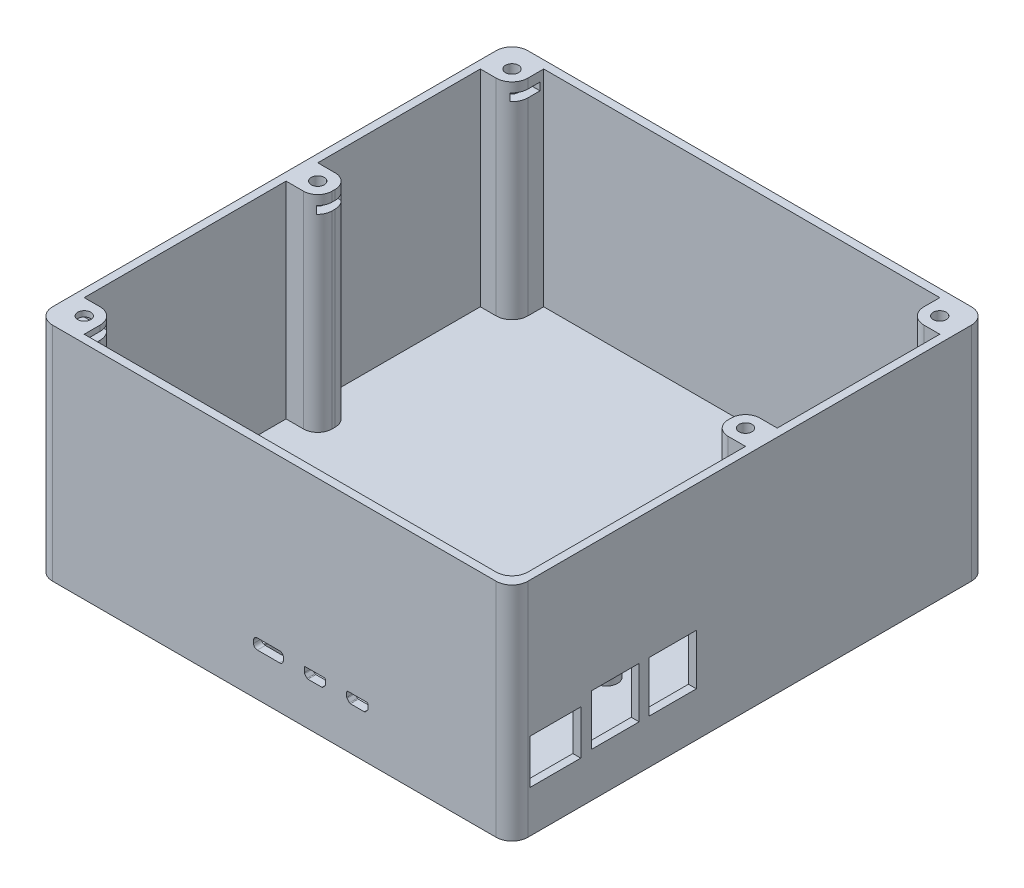
SolidWorks part; units mm, degrees
ref_plane "Alzado" through (0, 0, 0) normal (0, 0, 1) x (1, 0, 0)
ref_plane "Planta" through (0, 0, 0) normal (0, 1, 0) x (1, 0, 0)
ref_plane "Vista lateral" through (0, 0, 0) normal (1, 0, 0) x (0, 0, -1)
sketch "Croquis2" plane through (0, 0, 0) normal (0, 1, 0) x (1, 0, 0)
  line L1 (-75, -75) -> (75, -75)
  line L2 (-75, -75) -> (-75, 75)
  line L3 (-75, 75) -> (75, 75)
  line L4 (75, -75) -> (75, 75)
  line L5 (-75, -75) -> (75, 75) construction
  line L6 (-75, 75) -> (75, -75) construction
  point P0 (0, 0)
extrude "Saliente-Extruir1" add sketch "Croquis2" along normal blind 70
sketch "Croquis3" plane through (0, 70, 0) normal (0, 1, 0) x (1, 0, 0)
  line L1 (-72.5, -72.5) -> (72.5, -72.5)
  line L2 (-72.5, -72.5) -> (-72.5, 72.5)
  line L3 (-72.5, 72.5) -> (72.5, 72.5)
  line L4 (72.5, -72.5) -> (72.5, 72.5)
  line L5 (-72.5, -72.5) -> (72.5, 72.5) construction
  line L6 (-72.5, 72.5) -> (72.5, -72.5) construction
  point P0 (0, 0)
  dimension "D1" = 145
  dimension "D2" = 145
extrude "Cortar-Extruir1" cut sketch "Croquis3" against normal blind 65
sketch "Croquis4" plane through (0, 5, 0) normal (0, 1, 0) x (1, 0, 0)
  line L0 (-9.4, -67.8) -> (48.6, -67.8) construction
  line L2 (-9.4, -67.8) -> (-9.4, -18.8) construction
  line L3 (48.6, -18.8) -> (72.5, -18.8) construction
  line L4 (-72.5, -72.5) -> (72.5, -72.5) construction
  line L6 (72.5, -72.5) -> (72.5, 72.5) construction
  circle A0 centre (-9.4, -67.8) radius 3.5
  circle A1 centre (48.6, -67.8) radius 3.5
  circle A2 centre (-9.4, -18.8) radius 3.5
  circle A3 centre (48.6, -18.8) radius 3.5
  dimension "D1" = 4.7
  dimension "D2" = 7
  dimension "D3" = 23.9
  dimension "D5" = 58
  dimension "D6" = 49
extrude "Saliente-Extruir3" add sketch "Croquis4" along normal blind 7
sketch "Croquis5" plane through (0, 12, 0) normal (0, 1, 0) x (1, 0, 0)
  circle A0 centre (-9.4, -18.8) radius 1.4
  circle A1 centre (48.6, -18.8) radius 1.4
  circle A2 centre (-9.4, -67.8) radius 1.4
  circle A3 centre (48.6, -67.8) radius 1.4
  dimension "D1" = 2.8
extrude "Cortar-Extruir2" cut sketch "Croquis5" against normal blind 6
sketch "Croquis7" plane through (75, 0, 0) normal (1, 0, 0) x (0, 0, -1)
  line L0 (-75, 0) -> (-75, 13.3) construction
  line L1 (-75, 70) -> (-75, 0) construction
  line L2 (-75, 13.3) -> (-69.3, 13.3) construction
  line L3 (-75, 0) -> (75, 0) construction
  line L4 (-69.3, 13.3) -> (-53.3, 13.3)
  line L5 (-69.3, 13.3) -> (-69.3, 27.3)
  line L6 (-69.3, 27.3) -> (-53.3, 27.3)
  line L7 (-53.3, 13.3) -> (-53.3, 27.3)
  line L8 (-34.866, 14) -> (-31.816, 14) construction
  line L9 (-49.866, 14) -> (-34.866, 14)
  line L10 (-49.866, 14) -> (-49.866, 30)
  line L11 (-49.866, 30) -> (-34.866, 30)
  line L12 (-34.866, 14) -> (-34.866, 30)
  line L14 (-31.816, 14) -> (-16.816, 14)
  line L15 (-31.816, 14) -> (-31.816, 30)
  line L16 (-31.816, 30) -> (-16.816, 30)
  line L17 (-16.816, 14) -> (-16.816, 30)
  dimension "D1" = 13.3
  dimension "D2" = 5.7
  dimension "D3" = 16
  dimension "D4" = 14
  dimension "D5" = 3.434
  dimension "D6" = 15
  dimension "D7" = 16
  dimension "D8" = 3.05
  dimension "D9" = 16
  dimension "D10" = 15
  dimension "D11" = 14
extrude "Cortar-Extruir3" cut sketch "Croquis7" against normal up to next
sketch "Croquis8" plane through (0, 0, 75) normal (0, 0, 1) x (1, 0, 0)
  line L0 (75, 0) -> (72.5, 0) construction
  line L1 (-75, 0) -> (75, 0) construction
  line L2 (72.5, 0) -> (29.3, 0) construction
  line L3 (29.3, 0) -> (22.6, 0) construction
  line L8 (75, 0) -> (75, 13.52) construction
  line L9 (75, 70) -> (75, 0) construction
  line L10 (75, 13.52) -> (-6.55, 13.52) construction
  line L12 (24.0214, 13.52) -> (28.3786, 13.52)
  line L13 (22.85, 14.73) -> (22.85, 16.12)
  line L14 (23.25, 16.52) -> (29.15, 16.52)
  line L15 (29.55, 14.73) -> (29.55, 16.12)
  line L16 (22.9603, 14.4541) -> (23.7318, 13.6441)
  line L17 (28.6682, 13.6441) -> (29.4397, 14.4541)
  line L24 (9.5603, 14.4541) -> (10.3318, 13.6441)
  line L25 (10.6214, 13.52) -> (14.9786, 13.52)
  line L26 (9.45, 14.73) -> (9.45, 16.12)
  line L27 (9.85, 16.52) -> (15.75, 16.52)
  line L28 (16.15, 14.73) -> (16.15, 16.12)
  line L29 (15.2682, 13.6441) -> (16.0397, 14.4541)
  line L31 (-5.35, 13.52) -> (1.65, 13.52)
  line L32 (-6.55, 14.72) -> (-6.55, 15.62)
  line L33 (-5.35, 16.82) -> (1.65, 16.82)
  line L34 (2.85, 14.72) -> (2.85, 15.62)
  arc A0 (29.15, 16.52) -> (29.55, 16.12) centre (29.15, 16.12) cw
  arc A1 (22.85, 16.12) -> (23.25, 16.52) centre (23.25, 16.12) cw
  arc A2 (29.4397, 14.4541) -> (29.55, 14.73) centre (29.15, 14.73) ccw
  arc A3 (28.6682, 13.6441) -> (28.3786, 13.52) centre (28.3786, 13.92) cw
  arc A4 (23.7318, 13.6441) -> (24.0214, 13.52) centre (24.0214, 13.92) ccw
  arc A5 (22.9603, 14.4541) -> (22.85, 14.73) centre (23.25, 14.73) cw
  arc A6 (9.5603, 14.4541) -> (9.45, 14.73) centre (9.85, 14.73) cw
  arc A7 (10.3318, 13.6441) -> (10.6214, 13.52) centre (10.6214, 13.92) ccw
  arc A8 (15.2682, 13.6441) -> (14.9786, 13.52) centre (14.9786, 13.92) cw
  arc A9 (16.0397, 14.4541) -> (16.15, 14.73) centre (15.75, 14.73) ccw
  arc A10 (15.75, 16.52) -> (16.15, 16.12) centre (15.75, 16.12) cw
  arc A11 (9.45, 16.12) -> (9.85, 16.52) centre (9.85, 16.12) cw
  arc A12 (1.65, 16.82) -> (2.85, 15.62) centre (1.65, 15.62) cw
  arc A13 (1.65, 13.52) -> (2.85, 14.72) centre (1.65, 14.72) ccw
  arc A14 (-5.35, 13.52) -> (-6.55, 14.72) centre (-5.35, 14.72) cw
  arc A15 (-6.55, 15.62) -> (-5.35, 16.82) centre (-5.35, 15.62) cw
  point P5 (22.85, 13.52)
  point P18 (29.55, 13.52)
  point P25 (29.55, 16.52)
  point P28 (22.85, 16.52)
  point P31 (29.55, 14.57)
  point P34 (28.55, 13.52)
  point P37 (23.85, 13.52)
  point P40 (22.85, 14.57)
  point P41 (9.45, 13.52)
  point P44 (16.15, 13.52)
  point P51 (9.45, 14.57)
  point P54 (10.45, 13.52)
  point P57 (15.15, 13.52)
  point P60 (16.15, 14.57)
  point P70 (2.85, 16.82)
  point P78 (-6.55, 16.82)
  dimension "D16" = 0.4
  dimension "D17" = 0.4
  dimension "D22" = 0.4
  dimension "D28" = 1.2
  dimension "D1" = 2.5
  dimension "D2" = 43.2
  dimension "D3" = 6.7
  dimension "D4" = 45.45
  dimension "D5" = 6.7
  dimension "D6" = 3
  dimension "D7" = 6.6
  dimension "D8" = 13.52
  dimension "D9" = 3
  dimension "D10" = 6.7
  dimension "D11" = 9.4
  dimension "D12" = 1
  dimension "D13" = 1.05
  dimension "D14" = 1
  dimension "D15" = 1.05
  dimension "D18" = 1
  dimension "D19" = 1.05
  dimension "D20" = 1
  dimension "D21" = 1.05
  dimension "D23" = 5.9
  dimension "D25" = 3.3
extrude "Cortar-Extruir4" cut sketch "Croquis8" against normal up to next
sketch "Croquis9" plane through (0, 5, 0) normal (0, 1, 0) x (1, 0, 0)
  line L0 (72.5, -72.5) -> (72.5, 72.5) construction
  line L1 (-72.5, -72.5) -> (-62.5, -72.5)
  line L4 (-72.5, -72.5) -> (-72.5, -62.5)
  line L7 (-72.5, -62.5) -> (-67.5, -62.5)
  line L8 (-62.5, -72.5) -> (-62.5, -67.5)
  line L9 (-72.5, 72.5) -> (-62.5, 72.5)
  line L10 (-72.5, 72.5) -> (-72.5, 62.5)
  line L13 (-72.5, 62.5) -> (-67.5, 62.5)
  line L15 (-62.5, 72.5) -> (-62.5, 67.5)
  line L16 (-72.5, 72.5) -> (-72.5, -72.5) construction
  line L17 (72.5, 72.5) -> (62.5, 72.5)
  line L18 (72.5, 72.5) -> (72.5, 62.5)
  line L19 (72.5, 62.5) -> (67.5, 62.5)
  line L20 (62.5, 72.5) -> (62.5, 67.5)
  line L21 (72.5, 1.2) -> (67, 1.2)
  line L22 (72.5, 1.2) -> (72.5, 11.2)
  line L23 (72.5, 11.2) -> (67, 11.2)
  line L24 (62.5, 5.7) -> (62.5, 6.7)
  line L25 (-72.5, 1.2) -> (-67, 1.2)
  line L26 (-72.5, 1.2) -> (-72.5, 11.2)
  line L27 (-72.5, 11.2) -> (-67, 11.2)
  line L28 (-62.5, 5.7) -> (-62.5, 6.7)
  arc A0 (-67.5, 62.5) -> (-62.5, 67.5) centre (-67.5, 67.5) ccw
  arc A1 (67.5, 62.5) -> (62.5, 67.5) centre (67.5, 67.5) cw
  circle A2 centre (48.6, -18.8) radius 1.4 construction
  arc A3 (67, 1.2) -> (62.5, 5.7) centre (67, 5.7) cw
  arc A4 (67, 11.2) -> (62.5, 6.7) centre (67, 6.7) ccw
  arc A5 (-67.5, -62.5) -> (-62.5, -67.5) centre (-67.5, -67.5) cw
  arc A6 (-67, 1.2) -> (-62.5, 5.7) centre (-67, 5.7) ccw
  arc A7 (-67, 11.2) -> (-62.5, 6.7) centre (-67, 6.7) cw
  circle A8 centre (-9.4, -18.8) radius 1.4 construction
  point P20 (-62.5, 62.5)
  point P23 (62.5, 62.5)
  point P28 (62.5, 1.2)
  point P31 (62.5, 11.2)
  point P34 (-62.5, -62.5)
  point P46 (-62.5, 1.2)
  point P49 (-62.5, 11.2)
  dimension "D1" = 10
  dimension "D2" = 10
  dimension "D3" = 5
  dimension "D5" = 5
  dimension "D9" = 4.5
  dimension "D12" = 5
  dimension "D15" = 4.5
  dimension "D4" = 10
  dimension "D6" = 10
  dimension "D7" = 10
  dimension "D8" = 20
  dimension "D10" = 10
  dimension "D11" = 10
  dimension "D13" = 10
  dimension "D14" = 10
  dimension "D16" = 20
extrude "Saliente-Extruir4" add sketch "Croquis9" along normal through all
sketch "Croquis10" plane through (0, 70, 0) normal (0, 1, 0) x (1, 0, 0)
  line L0 (-75, 75) -> (-75, -75) construction
  line L1 (75, -75) -> (75, 75) construction
  circle A0 centre (-67.5, 67.5) radius 2.05
  circle A2 centre (-67.5, 6.2) radius 2.05
  circle A3 centre (-67.5, -67.5) radius 2.05
  circle A4 centre (67.5, 67.5) radius 2.05
  circle A5 centre (67.5, 6.2) radius 2.05
  dimension "D1" = 4.1
  dimension "D2" = 61.3
  dimension "D3" = 7.5
  dimension "D4" = 7.5
  dimension "D5" = 61.3
extrude "Cortar-Extruir5" cut sketch "Croquis10" against normal blind 15
sketch "Croquis11" plane through (-62.5, 0, 0) normal (1, 0, 0) x (0, 0, -1)
  line L0 (5.7, 70) -> (6.7, 70) construction
  line L1 (71.35, 67) -> (63.65, 67)
  line L2 (71.35, 67) -> (71.35, 64.6)
  line L3 (71.35, 64.6) -> (63.65, 64.6)
  line L4 (63.65, 67) -> (63.65, 64.6)
  line L5 (67.5, 70) -> (72.5, 70) construction
  line L6 (2.35, 64.6) -> (10.05, 64.6)
  line L7 (2.35, 64.6) -> (2.35, 67)
  line L8 (2.35, 67) -> (10.05, 67)
  line L9 (10.05, 64.6) -> (10.05, 67)
  line L10 (11.2, 70) -> (6.7, 70) construction
  line L11 (-72.5, 70) -> (-67.5, 70) construction
  line L12 (-71.35, 65.8576) -> (-63.65, 65.8576)
  line L13 (-71.35, 65.8576) -> (-71.35, 68.2576)
  line L14 (-71.35, 68.2576) -> (-63.65, 68.2576)
  line L15 (-63.65, 65.8576) -> (-63.65, 68.2576)
  point P4 (67.5, 67)
  point P14 (6.2, 70)
  point P15 (6.2, 67)
  point P22 (-67.5, 68.2576)
  dimension "D1" = 2.4
  dimension "D2" = 7.7
  dimension "D3" = 3
  dimension "D4" = 2.4
  dimension "D5" = 7.7
  dimension "D6" = 3
  dimension "D7" = 2.4
  dimension "D8" = 7.7
  dimension "D9" = 1.7424
extrude "Cortar-Extruir6" cut sketch "Croquis11" against normal blind 10
sketch "Croquis12" plane through (62.5, 0, 0) normal (-1, 0, 0) x (0, 0, 1)
  line L0 (-72.5, 70) -> (-67.5, 70) construction
  line L1 (-71.35, 64.6) -> (-63.65, 64.6)
  line L2 (-71.35, 64.6) -> (-71.35, 67)
  line L3 (-71.35, 67) -> (-63.65, 67)
  line L4 (-63.65, 64.6) -> (-63.65, 67)
  line L5 (-6.7, 70) -> (-5.7, 70) construction
  line L6 (-10.05, 64.6) -> (-2.35, 64.6)
  line L7 (-10.05, 64.6) -> (-10.05, 67)
  line L8 (-10.05, 67) -> (-2.35, 67)
  line L9 (-2.35, 64.6) -> (-2.35, 67)
  point P4 (-67.5, 67)
  point P14 (-6.2, 70)
  point P15 (-6.2, 67)
  dimension "D1" = 2.4
  dimension "D2" = 7.7
  dimension "D3" = 3
  dimension "D4" = 2.4
  dimension "D5" = 7.7
  dimension "D6" = 3
extrude "Cortar-Extruir7" cut sketch "Croquis12" against normal blind 10
fillet "Redondeo1" radius 5 4 edges at (75, 35, -75) (75, 35, 75) (-75, 35, 75) (-75, 35, -75)
fillet "Redondeo2" radius 5 1 edges at (72.5, 37.5, 72.5)
ref_axis "eje_base" through (0, 34.9552, 0) along (0, 1, 0)
